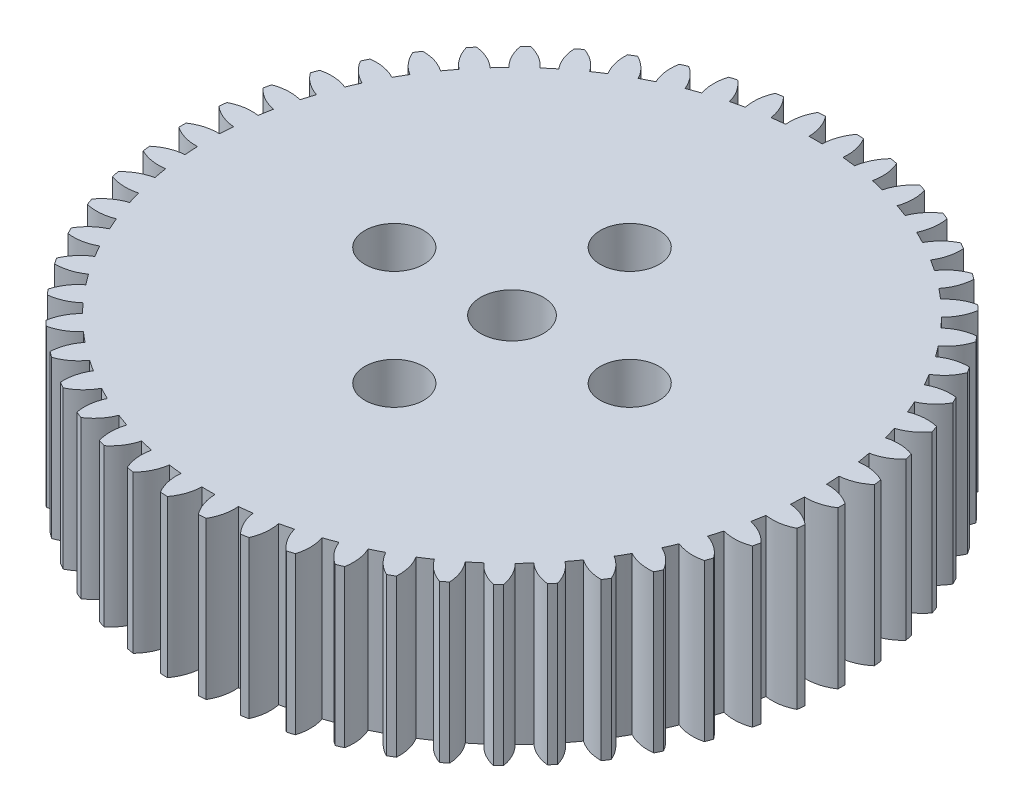
SolidWorks part; units mm, degrees
ref_plane "Ebene vorne" through (0, 0, 0) normal (0, 0, 1) x (1, 0, 0)
ref_plane "Ebene oben" through (0, 0, 0) normal (0, 1, 0) x (1, 0, 0)
ref_plane "Ebene rechts" through (0, 0, 0) normal (1, 0, 0) x (0, 0, -1)
sketch "Skizze1" plane through (0, 0, 0) normal (0, 1, 0) x (1, 0, 0)
  circle A0 centre (0, 0) radius 16.8
  dimension "D1" = 33.6
extrude "Aufsatz-Linear austragen1" add sketch "Skizze1" along normal blind 8
sketch "Skizze2" plane through (0, 8, 0) normal (0, 1, 0) x (1, 0, 0)
  line L0 (0, 0) -> (0, 16.8) construction
  line L1 (0, 0) -> (-0.3367, 15.4763) construction
  line L2 (0, 0) -> (0.9768, 16.7716) construction
  line L3 (-0.4712, 16.1931) -> (0.4712, 16.1931) construction
  line L4 (0.4712, 16.1931) -> (1.4119, 16.1384) construction
  line L5 (0, 14.8986) -> (-0.6869, 16.786) construction
  circle A0 centre (0, 0) radius 16.8
  circle A1 centre (0, 0) radius 16.2 construction
  circle A2 centre (0, 0) radius 15.48
  arc A3 (-0.792, 16.7813) -> (-0.3367, 15.4763) centre (-2.5744, 15.4277) cw
  arc A4 (0.792, 16.7813) -> (0.3367, 15.4763) centre (2.5744, 15.4277) ccw
  dimension "D3" = 33.6
  dimension "D4" = 32.4
  dimension "D5" = 30.96
  dimension "D1" = 3.333
  dimension "D2" = 20
extrude "Schnitt-Linear austragen1" cut sketch "Skizze2" against normal blind 8 contours A4 A0 A3 A2 region at (0, 8, -16.2378)
pattern_circular "Kreismuster1" count 54 over 360 about axis through (0, 8, 0) along (0, -1, 0) of "Schnitt-Linear austragen1"
sketch "Skizze3" plane through (0, 0, 0) normal (0, -1, 0) x (1, 0, 0)
  circle A0 centre (0, 0) radius 1.6
  dimension "D1" = 3.2
extrude "Schnitt-Linear austragen2" cut sketch "Skizze3" against normal up to surface (8 mm away) up to face at (0, 8, 0)
sketch "Skizze4" plane through (0, 0, 0) normal (0, -1, 0) x (1, 0, 0)
  line L0 (0, 0) -> (0, 6) construction
  circle A0 centre (0, 6) radius 1.5
  circle A1 centre (6, 0) radius 1.5
  circle A2 centre (0, -6) radius 1.5
  circle A3 centre (-6, 0) radius 1.5
  point P13 (0, 0)
  dimension "D1" = 3
  dimension "D2" = 6
  dimension "D3" = 4
extrude "Schnitt-Linear austragen3" cut sketch "Skizze4" against normal through all
equation "\"Tooth\"= 54"
equation "\"module\"= 0.6"
equation "\"D1@Skizze1\"=\"module\"*(\"Tooth\"+2)"
